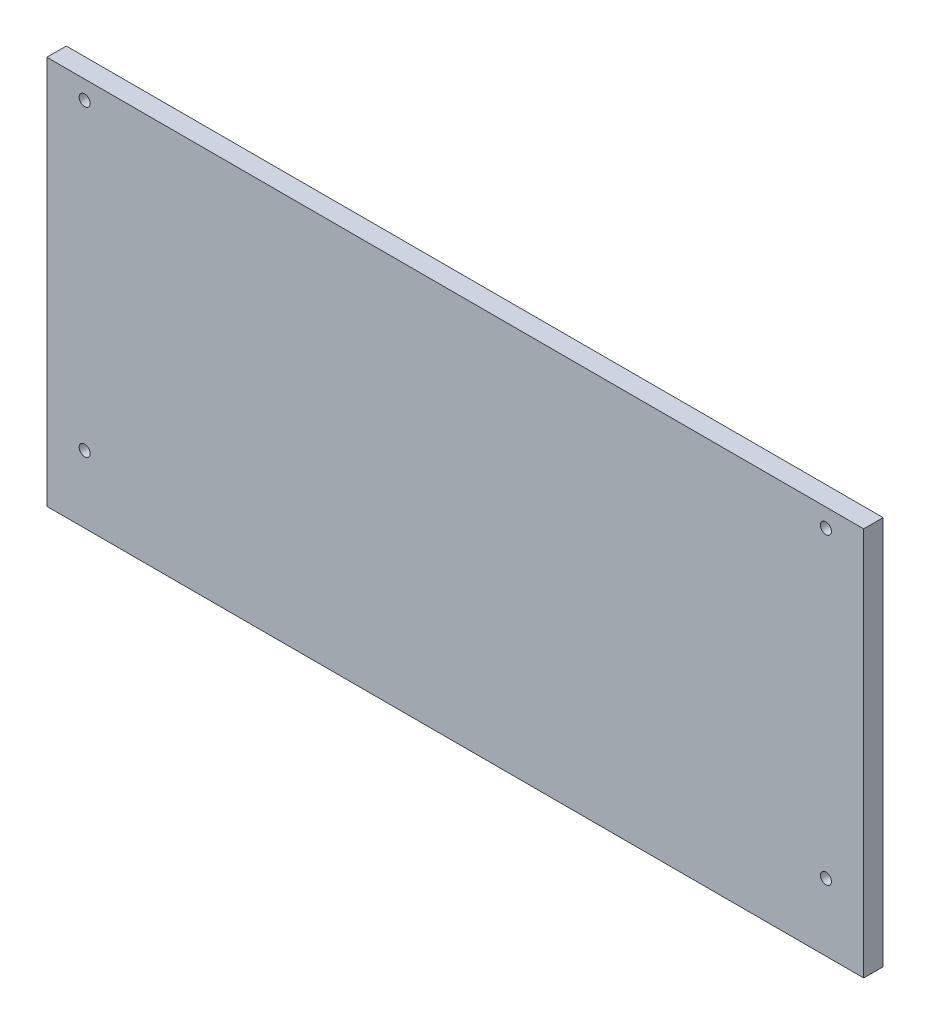
SolidWorks part; units mm, degrees
material "Acrylic (Medium-high impact)"
ref_plane "Front Plane" through (0, 0, 0) normal (0, 0, 1) x (1, 0, 0)
ref_plane "Top Plane" through (0, 0, 0) normal (0, 1, 0) x (1, 0, 0)
ref_plane "Right Plane" through (0, 0, 0) normal (1, 0, 0) x (0, 0, -1)
sketch "Sketch1" plane through (0, 0, 0) normal (0, 0, 1) x (1, 0, 0)
  line L1 (266.7, 127) -> (0, 127)
  line L2 (266.7, 127) -> (266.7, 0)
  line L3 (266.7, 0) -> (0, 0)
  line L4 (0, 127) -> (0, 0)
  line L5 (266.7, 127) -> (0, 0) construction
  line L6 (266.7, 0) -> (0, 127) construction
  point P0 (133.35, 63.5)
  dimension "D1" = 127
  dimension "D2" = 266.7
extrude "Boss-Extrude1" add sketch "Sketch1" along normal blind 6.35
hole_wizard "M3 Clearance Hole1" positions "Sketch2" profile "Sketch3" hole size "M3" standard "ANSI Metric" end condition through all
sketch "Sketch2" plane through (0, 0, 6.35) normal (0, 0, 1) x (1, 0, 0)
  line L0 (0, 127) -> (0, 0) construction
  line L1 (266.7, 127) -> (0, 127) construction
  line L2 (266.7, 0) -> (266.7, 127) construction
  line L3 (0, 0) -> (266.7, 0) construction
  point P0 (12.3444, 121.0056)
  point P2 (12.3444, 21.9964)
  point P4 (254.3556, 21.9964)
  point P6 (254.3556, 121.0056)
  dimension "D1" = 12.3444
  dimension "D2" = 5.9944
  dimension "D3" = 12.3444
  dimension "D4" = 21.9964
sketch "Sketch3" plane through (12.3444, 121.0056, 6.35) normal (1, 0, 0) x (0, -1, 0)
  line L0 (0, 0) -> (0, 6.35)
  line L1 (0, 6.35) -> (1.8, 6.35)
  line L2 (1.8, 6.35) -> (1.8, 0)
  line L5 (1.8, 0) -> (0, 0)
  line L11 (0, -6.35) -> (0, 107.95) construction
  dimension "Thru Hole Dia." = 3.6
  dimension "Thru Hole Depth" = 6.35
sketch "Sketch4" plane through (0, 0, 6.35) normal (0, 0, 1) x (1, 0, 0)
  line L0 (0, 127) -> (0, 0) construction
  line L1 (46.99, 107.95) -> (50.4952, 107.95)
  line L2 (46.99, 107.95) -> (46.99, 31.75)
  line L3 (46.99, 31.75) -> (50.4952, 31.75)
  line L4 (50.4952, 107.95) -> (50.4952, 31.75)
  line L5 (216.2048, 107.95) -> (219.71, 107.95)
  line L6 (216.2048, 107.95) -> (216.2048, 31.75)
  line L7 (216.2048, 31.75) -> (219.71, 31.75)
  line L8 (219.71, 107.95) -> (219.71, 31.75)
  line L9 (266.7, 0) -> (266.7, 127) construction
  line L10 (266.7, 127) -> (0, 127) construction
  dimension "D1" = 3.5052
  dimension "D2" = 76.2
  dimension "D3" = 46.99
  dimension "D4" = 46.99
  dimension "D5" = 19.05
extrude "Cut-Extrude1" [suppressed] cut sketch "Sketch4" against normal through all
sketch "Sketch5" plane through (0, 0, 6.35) normal (0, 0, 1) x (1, 0, 0)
  line L0 (0, 0) -> (266.7, 0)
  line L1 (266.7, 0) -> (266.7, 37.4822)
  line L2 (266.7, 0) -> (266.7, 127) construction
  line L3 (266.7, 37.4822) -> (0, 0)
  dimension "D1" = 8
extrude "Cut-Extrude2" [suppressed] cut sketch "Sketch5" against normal through all
